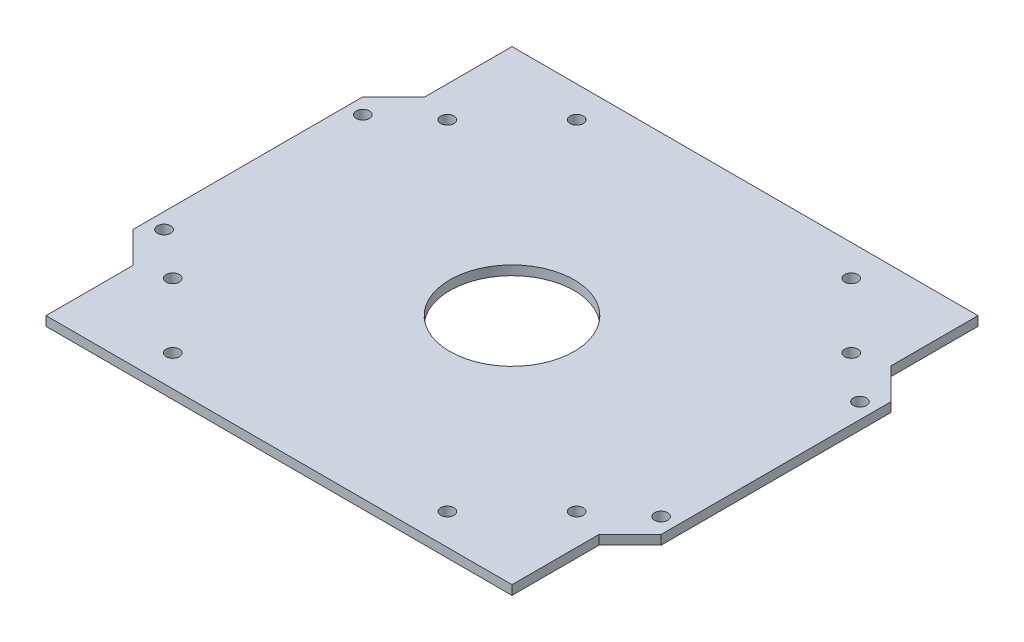
SolidWorks part; units mm, degrees
ref_plane "Front Plane" through (0, 0, 0) normal (0, 0, 1) x (1, 0, 0)
ref_plane "Top Plane" through (0, 0, 0) normal (0, 1, 0) x (1, 0, 0)
ref_plane "Right Plane" through (0, 0, 0) normal (1, 0, 0) x (0, 0, -1)
sketch "Sketch1" plane through (0, 0, 0) normal (0, 1, 0) x (1, 0, 0)
  line L1 (-75, -75) -> (75, -75)
  line L2 (-75, -75) -> (-75, 75)
  line L3 (-75, 75) -> (75, 75)
  line L4 (75, -75) -> (75, 75)
  line L5 (-75, -75) -> (75, 75) construction
  line L6 (-75, 75) -> (75, -75) construction
  point P0 (0, 0)
  dimension "D1" = 150
  dimension "D2" = 150
extrude "Boss-Extrude1" add sketch "Sketch1" along normal blind 3
sketch "Sketch2" plane through (0, 3, 0) normal (0, 1, 0) x (1, 0, 0)
  line L0 (75, 75) -> (55, 75) construction
  line L1 (-75, 75) -> (-55, 75) construction
  line L2 (-75, 75) -> (-75, 55) construction
  line L3 (-75, 55) -> (-55, 55) construction
  line L4 (-55, 75) -> (-55, 55) construction
  line L5 (75, 75) -> (75, 55) construction
  line L6 (75, 55) -> (55, 55) construction
  line L7 (55, 75) -> (55, 55) construction
  line L8 (75, -75) -> (75, -55) construction
  line L9 (75, -75) -> (55, -75) construction
  line L10 (55, -75) -> (55, -55) construction
  line L11 (75, -55) -> (55, -55) construction
  line L12 (-75, -75) -> (-55, -75) construction
  line L13 (-75, -75) -> (-75, -55) construction
  line L14 (-75, -55) -> (-55, -55) construction
  line L15 (-55, -75) -> (-55, -55) construction
  line L16 (-65, -75) -> (-65, 75) construction
  line L17 (-75, 0) -> (75, 0) construction
  line L18 (-75, 75) -> (-75, -75) construction
  line L19 (75, -75) -> (75, 75) construction
  circle A0 centre (-65, -44.2) radius 2.125
  circle A1 centre (-65, 44.2) radius 2.125
  circle A2 centre (-44.2, 65) radius 2.125
  circle A3 centre (44.2, 65) radius 2.125
  circle A4 centre (65, 44.2) radius 2.125
  circle A5 centre (65, -44.2) radius 2.125
  circle A6 centre (44.2, -65) radius 2.125
  circle A7 centre (-44.2, -65) radius 2.125
  circle A8 centre (0, 0) radius 20
  point P31 (75, 75)
  point P44 (0, 0)
  point P46 (0, 0)
  point P48 (0, 0)
  dimension "D4" = 4.25
  dimension "40" = 40
  dimension "D1" = 20
  dimension "D2" = 20
  dimension "D5" = 10.8
  dimension "D3" = 4
  dimension "D6" = 4
extrude "Cut-Extrude3" cut sketch "Sketch2" against normal through all
sketch "Sketch3" plane through (0, 3, 0) normal (0, 1, 0) x (1, 0, 0)
  line L0 (-85, 0) -> (-75, 0) construction
  line L1 (-85, -37) -> (-75, -37)
  line L2 (-85, -37) -> (-85, 37)
  line L3 (-85, 37) -> (-75, 37)
  line L5 (0, 75) -> (0, -75) construction
  line L6 (75, 75) -> (-75, 75) construction
  line L7 (-75, -75) -> (75, -75) construction
  line L8 (-75, -37) -> (-75, 37)
  line L9 (-75, 75) -> (-75, -75) construction
  line L10 (85, -37) -> (85, 37)
  line L11 (85, 37) -> (75, 37)
  line L12 (75, -37) -> (75, 37)
  line L13 (85, -37) -> (75, -37)
  circle A0 centre (-80, 32) radius 2.125
  circle A1 centre (-80, -32) radius 2.125
  circle A2 centre (80, -32) radius 2.125
  circle A3 centre (80, 32) radius 2.125
  point P0 (0, 0)
  dimension "D1" = 4.25
  dimension "D2" = 32
  dimension "D3" = 5
  dimension "D4" = 80
  dimension "D5" = 5
  dimension "D6" = 0
extrude "Boss-Extrude2" add sketch "Sketch3" against normal up to surface (3 mm away) up to face at (-65, 0, -46.325)
sketch "Sketch4" plane through (0, 3, 0) normal (0, 1, 0) x (1, 0, 0)
  line L0 (-85, 37) -> (-75, 47)
  line L1 (-75, 75) -> (-75, 37) construction
  line L2 (-75, 47) -> (-75, 37)
  line L3 (-75, 37) -> (-85, 37)
  line L4 (0, 75) -> (0, -75) construction
  line L5 (75, 75) -> (-75, 75) construction
  line L6 (-75, -75) -> (75, -75) construction
  line L7 (-85, 0) -> (85, 0) construction
  line L8 (-85, 37) -> (-85, -37) construction
  line L9 (85, -37) -> (85, 37) construction
  line L10 (75, 47) -> (75, 37)
  line L11 (85, 37) -> (75, 47)
  line L12 (75, 37) -> (85, 37)
  line L13 (85, -37) -> (75, -47)
  line L14 (75, -37) -> (85, -37)
  line L15 (75, -47) -> (75, -37)
  line L16 (-75, -47) -> (-75, -37)
  line L17 (-85, -37) -> (-75, -47)
  line L18 (-75, -37) -> (-85, -37)
  dimension "D1" = 10
extrude "Boss-Extrude3" add sketch "Sketch4" against normal up to surface (3 mm away) contours L10 L12 L11 | L3 L0 L2 | L13 L15 L14 | L16 L18 L17 up to face at (-65, 0, -46.325)
